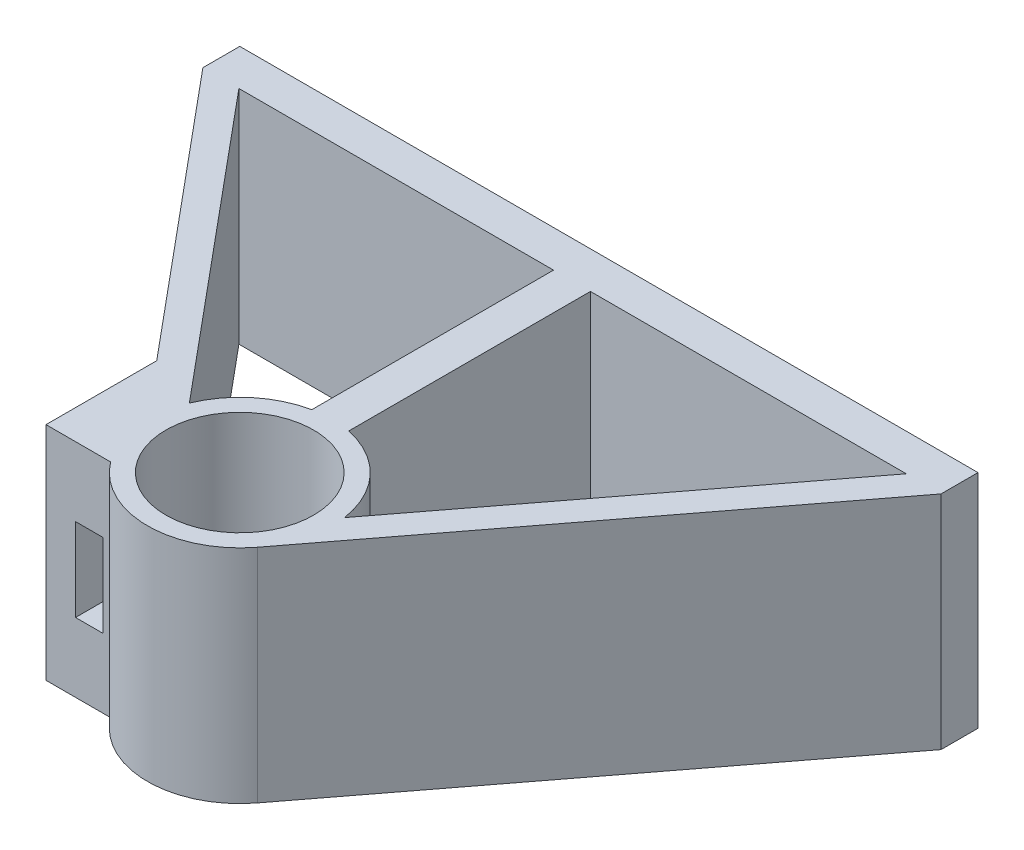
SolidWorks part; units mm, degrees
ref_plane "Front Plane" through (0, 0, 0) normal (0, 0, 1) x (1, 0, 0)
ref_plane "Top Plane" through (0, 0, 0) normal (0, 1, 0) x (1, 0, 0)
ref_plane "Right Plane" through (0, 0, 0) normal (1, 0, 0) x (0, 0, -1)
sketch "Sketch1" plane through (0, 0, 0) normal (0, 1, 0) x (1, 0, 0)
  line L0 (0, 0) -> (-14.5636, 0) construction
  line L2 (-7.5, 3) -> (-7.5, -3)
  line L3 (-4, -3) -> (-7.5, -3)
  line L16 (0, 29.2496) -> (0, -23.3028) construction
  line L17 (20, 20) -> (-20, 20)
  line L18 (20, 20) -> (20, 18)
  line L19 (20, 18) -> (3.9772, -3.0302)
  line L20 (-20, 20) -> (-20, 18)
  line L21 (-20, 18) -> (-7.5, 3)
  line L22 (-18.0474, 18) -> (-1, 18)
  line L23 (-1, 18) -> (-1, 4.899)
  line L24 (1, 4.899) -> (1, 18)
  line L25 (1, 18) -> (18.1142, 18)
  line L26 (18.1142, 18) -> (4.948, 0.7191)
  line L27 (-18.0474, 18) -> (-4.6269, 1.8953)
  circle A0 centre (0, 0) radius 4
  arc A5 (-4, -3) -> (3.9772, -3.0302) centre (0, 0) ccw
  arc A6 (-1, 4.899) -> (-4.6269, 1.8953) centre (0, 0) ccw
  arc A7 (4.948, 0.7191) -> (1, 4.899) centre (0, 0) ccw
  point P4 (-6.435, -4.7236)
  point P10 (-7.5, 0)
  point P15 (0, 20)
  point P26 (-1.9948, -4.5848)
  dimension "D1" = 1
  dimension "D2" = 40
  dimension "D10" = 8
  dimension "D3" = 6
  dimension "D4" = 7.5
  dimension "D5" = 2
  dimension "D6" = 1.5
  dimension "D7" = 20
  dimension "D8" = 1.5
  dimension "D9" = 2
extrude "Boss-Extrude1" add sketch "Sketch1" along normal blind 6 and the other way blind 6
sketch "Sketch2" plane through (0, 0, 3) normal (0, 0, -1) x (-1, 0, 0)
  line L0 (-6.9549, 0) -> (16.7857, 0) construction
  line L1 (4.4, -2.25) -> (4.4, 2.25)
  line L2 (4.4, 2.25) -> (5.9, 2.25)
  line L3 (5.9, 2.25) -> (5.9, -2.25)
  line L4 (4.4, -2.25) -> (5.9, -2.25)
  point P8 (5.9, 0)
  point P9 (4.4, 0)
  dimension "D1" = 4.5
  dimension "D2" = 4.4
  dimension "D3" = 1.5
extrude "Cut-Extrude1" cut sketch "Sketch2" along normal up to next
